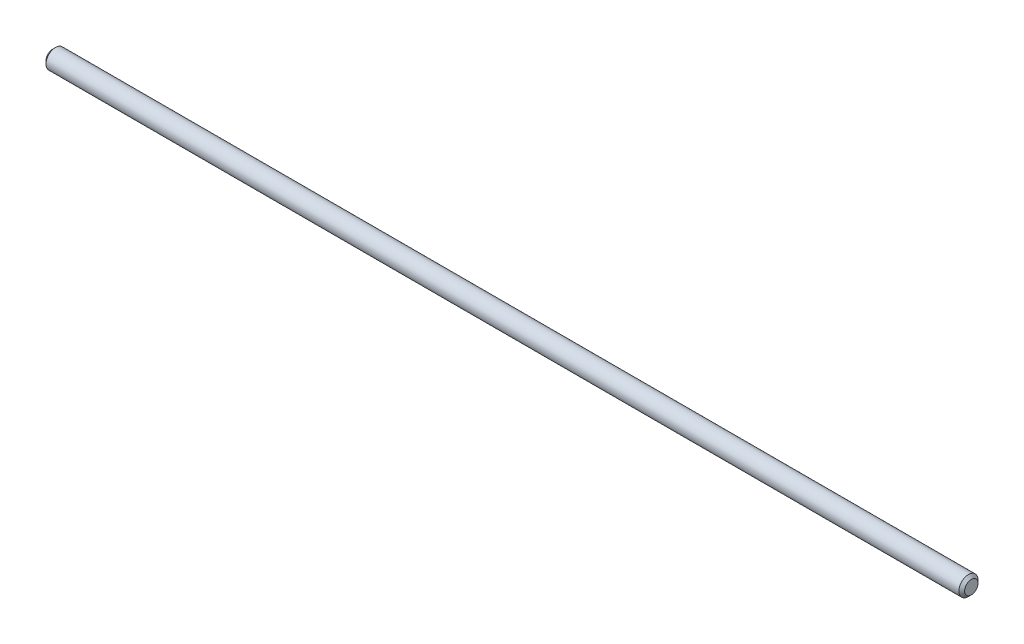
SolidWorks part; units mm, degrees
ref_plane "Front Plane" through (0, 0, 0) normal (0, 0, 1) x (1, 0, 0)
ref_plane "Top Plane" through (0, 0, 0) normal (0, 1, 0) x (1, 0, 0)
ref_plane "Right Plane" through (0, 0, 0) normal (1, 0, 0) x (0, 0, -1)
sketch "Sketch1" plane through (0, 0, 0) normal (0, 0, 1) x (1, 0, 0)
  line L0 (-152.4, 0) -> (152.4, 0) construction
  line L1 (152.4, 3.175) -> (152.4, -3.175) construction
  line L2 (-152.4, 3.175) -> (-152.4, -3.175) construction
  point P6 (147.955, -3.175)
  dimension "Thread Diameter" = 6.35
  dimension "Length" = 304.8
  dimension "D1" = 4.445
sketch "Sketch2" plane through (0, 0, 0) normal (1, 0, 0) x (0, 0, -1)
  circle A0 centre (0, 0) radius 3.175
extrude "Boss-Extrude1" add sketch "Sketch2" against normal up to vertex (152.4 mm away) and the other way up to vertex (152.4 mm away) up to point (-152.4, 0, 0) other way up to point (152.4, 0, 0)
cosmetic thread "Cosmetic Thread1" parameters "D2"=4.8387
sketch "Sketch3" plane through (152.4, 0, 0) normal (1, 0, 0) x (0, 0, -1)
  circle A1 centre (0, 0) radius 3.175
  circle A2 centre (0, 0) radius 3.175
  dimension "D1" = 0
curve "Helix/Spiral1" pitch 1.27 height 306.07 turns 241 parameters "Pitch"=1.27
chamfer "Chamfer1" distance 0.9525 angle 45 2 edges at (-152.4, 0, -3.175) (152.4, 0, -3.175)
sketch "Sketch4" plane through (0, 0, 0) normal (0, 0, 1) x (1, 0, 0)
  line L0 (152.3206, 3.3125) -> (152.9556, 2.2126) construction
  line L1 (152.9556, 2.2126) -> (153.5906, 3.3125) construction
  line L2 (153.5906, 3.3125) -> (152.3206, 3.3125) construction
  line L3 (152.9556, 3.3125) -> (152.9556, 3.175) construction
  line L4 (152.9556, 2.2126) -> (152.9556, 2.3501) construction
  line L5 (152.8763, 2.3501) -> (153.035, 2.3501) construction
  line L6 (152.4, 3.175) -> (153.5113, 3.175) construction
  line L7 (152.8763, 2.3501) -> (152.3603, 3.2437)
  line L8 (152.8763, 2.3501) -> (153.035, 2.3501)
  line L9 (152.3603, 3.2437) -> (153.5509, 3.2437)
  line L10 (153.5509, 3.2437) -> (153.035, 2.3501)
  point P13 (152.9556, 3.2437)
  dimension "D2" = 0.1588
sweep "Cut-Sweep3" [suppressed] cut profiles "Sketch4" path "Helix/Spiral1"
equation "\"D3@Helix/Spiral1\" = \"Length@Sketch1\"+\"Pitch@Helix/Spiral1\""
equation "\"D1@Chamfer1\" = \"Pitch@Helix/Spiral1\"*.75"
equation "\"D1@Sketch4\" = \"Pitch@Helix/Spiral1\""
equation "\"D2@Sketch4\" = \"D1@Sketch4\"/8"
equation "\"D1@Sketch1\" = \"Pitch@Helix/Spiral1\"*3.50"
